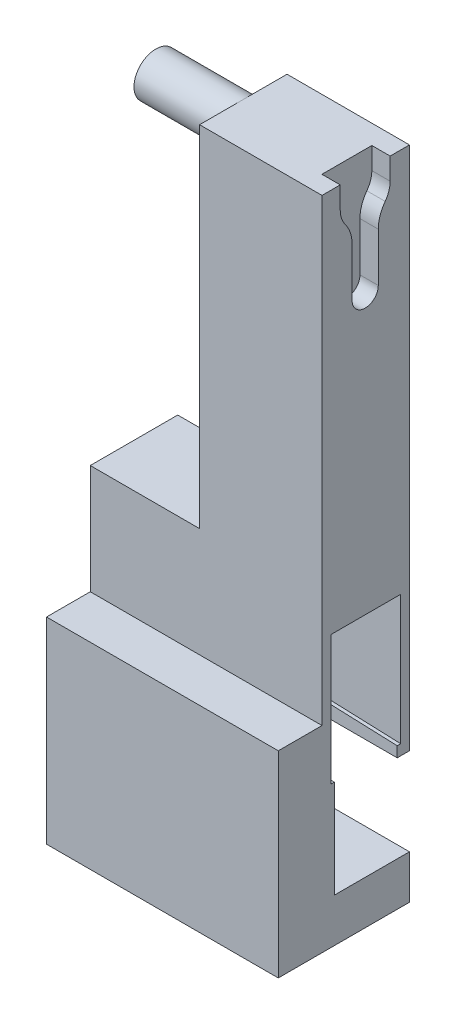
SolidWorks part; units mm, degrees
ref_plane "Front Plane" through (0, 0, 0) normal (0, 0, 1) x (1, 0, 0)
ref_plane "Top Plane" through (0, 0, 0) normal (0, 1, 0) x (1, 0, 0)
ref_plane "Right Plane" through (0, 0, 0) normal (1, 0, 0) x (0, 0, -1)
sketch "Sketch1" plane through (0, 0, 0) normal (0, 1, 0) x (1, 0, 0)
  line L1 (-17.78, -12.7) -> (17.78, -12.7)
  line L2 (-17.78, -12.7) -> (-17.78, 12.7)
  line L3 (-17.78, 12.7) -> (17.78, 12.7)
  line L4 (17.78, -12.7) -> (17.78, 12.7)
  line L5 (-17.78, -12.7) -> (17.78, 12.7) construction
  line L6 (-17.78, 12.7) -> (17.78, -12.7) construction
  point P0 (0, 0)
  dimension "D1" = 25.4
  dimension "D2" = 35.56
extrude "Boss-Extrude1" add sketch "Sketch1" along normal mid plane 50.8
sketch "Sketch2" plane through (-17.78, 0, 0) normal (-1, 0, 0) x (0, 0, 1)
  line L0 (-12.7, 25.4) -> (12.7, 25.4) construction
  circle A0 centre (0, 19.05) radius 6.35
  dimension "D1" = 12.7
extrude "Boss-Extrude2" add sketch "Sketch2" along normal mid plane 50.8
sketch "Sketch7" plane through (0, -25.4, 0) normal (0, -1, 0) x (1, 0, 0)
  line L1 (-17.78, 12.7) -> (17.78, 12.7)
  line L2 (-17.78, 12.7) -> (-17.78, -12.7)
  line L3 (-17.78, -12.7) -> (17.78, -12.7)
  line L4 (17.78, 12.7) -> (17.78, -12.7)
extrude "Boss-Extrude3" add sketch "Sketch7" along normal blind 101.6
sketch "Sketch10" plane through (-17.78, 0, 0) normal (-1, 0, 0) x (0, 0, 1)
  line L0 (12.7, 25.4) -> (12.7, -127) construction
  line L1 (-12.7, -127) -> (12.7, -127)
  line L2 (-12.7, -127) -> (-12.7, -76.2)
  line L3 (-12.7, -76.2) -> (12.7, -76.2)
  line L4 (12.7, -127) -> (12.7, -76.2)
  dimension "D1" = 50.8
extrude "Boss-Extrude4" add sketch "Sketch10" along normal blind 31.75
sketch "Sketch11" plane through (17.78, 0, 0) normal (1, 0, 0) x (0, 0, -1)
  line L0 (12.7, 25.4) -> (12.7, -127) construction
  line L1 (-12.7, -127) -> (12.7, -127)
  line L2 (-12.7, -127) -> (-12.7, -76.2)
  line L3 (-12.7, -76.2) -> (12.7, -76.2)
  line L4 (12.7, -127) -> (12.7, -76.2)
  line L5 (-10.16, -123.952) -> (-12.7, -127) construction
  line L6 (-10.16, -123.952) -> (10.16, -123.952)
  line L7 (-10.16, -123.952) -> (-10.16, -86.36)
  line L8 (-10.16, -86.36) -> (10.16, -86.36)
  line L9 (10.16, -123.952) -> (10.16, -86.36)
  line L10 (10.16, -123.952) -> (12.7, -127) construction
  dimension "D1" = 50.8
  dimension "D2" = 3.048
  dimension "D3" = 20.32
  dimension "D4" = 37.592
extrude "Cut-Extrude3" cut sketch "Sketch11" against normal blind 49.53 contours L6 L9 L8 L7 region at (17.78, -105.156, 0)
sketch "Sketch12" plane through (17.78, 0, 0) normal (1, 0, 0) x (0, 0, -1)
  line L0 (-3.96, 8.728) -> (-3.96, -5.422) construction
  line L1 (3.64, -5.422) -> (3.64, 8.728) construction
  line L2 (-3.96, 8.728) -> (-3.96, -5.422)
  line L3 (3.64, -5.422) -> (3.64, 8.728)
  line L4 (7.09, 19.078) -> (7.09, 26.328)
  line L5 (7.09, 26.328) -> (-0.16, 26.328)
  line L6 (-7.41, 19.078) -> (-7.41, 26.328)
  line L7 (-7.41, 26.328) -> (-0.16, 26.328)
  arc A0 (5.64, 14.728) -> (0.34, 26.3107) centre (-0.16, 19.078) ccw construction
  arc A1 (-0.66, 26.3107) -> (-5.96, 14.728) centre (-0.16, 19.078) ccw construction
  arc A2 (-3.96, 8.728) -> (-5.96, 14.728) centre (-13.96, 8.728) ccw construction
  arc A3 (-3.96, -5.422) -> (3.64, -5.422) centre (-0.16, -5.422) ccw construction
  arc A4 (5.64, 14.728) -> (3.64, 8.728) centre (13.64, 8.728) ccw construction
  arc A5 (5.64, 14.728) -> (-0.16, 26.328) centre (-0.16, 19.078) ccw
  arc A6 (-0.16, 26.328) -> (-5.96, 14.728) centre (-0.16, 19.078) ccw
  arc A7 (-3.96, 8.728) -> (-5.96, 14.728) centre (-13.96, 8.728) ccw
  arc A8 (-3.96, -5.422) -> (3.64, -5.422) centre (-0.16, -5.422) ccw
  arc A9 (5.64, 14.728) -> (3.64, 8.728) centre (13.64, 8.728) ccw
  circle A10 centre (-0.16, -5.422) radius 1.3954 construction
  circle A11 centre (-0.16, -1.422) radius 1.3954 construction
  circle A12 centre (-0.16, -5.422) radius 1.3954
  circle A13 centre (-0.16, -1.422) radius 1.3954
  line M15 (12.7, 25.4) -> (-12.7, 25.4)
extrude "Cut-Extrude4" cut sketch "Sketch12" against normal up to surface (5.32 mm away) contours A9 A5 A6 A7 L2 A8 L3 M15 | A6 L6 M15 | A5 L4 M15 region at (17.78, 11.0681, 0.16) region at (17.78, 23.9112, 6.3737) region at (17.78, 23.9112, -6.0537)
extrude "Cut-Extrude5" cut sketch "Sketch12<3>" against normal offset from surface (11.67 mm away) 6.35 contours A13 | A12 region at (17.78, -5.422, 0.16) region at (17.78, -1.422, 0.16) up to face at (12.46, -2.8174, 0.16)
sketch "Sketch12<3>" plane through (17.78, 0, 0) normal (1, 0, 0) x (0, 0, -1) same geometry as "Sketch12"
sketch "Sketch14" plane through (0, 0, -10.16) normal (0, 0, 1) x (1, 0, 0)
  line L0 (17.78, -123.952) -> (-31.75, -123.952)
  line L1 (-31.75, -123.952) -> (-31.75, -122.0925)
  line L2 (-31.75, -123.952) -> (-31.75, -86.36) construction
  line L3 (-31.75, -122.0925) -> (17.78, -123.952)
  dimension "D1" = 177.85
extrude "Boss-Extrude5" add sketch "Sketch14" along normal up to surface (20.32 mm away) up to face at (-6.985, -105.156, 10.16)
sketch "Sketch16" plane through (17.78, 0, 0) normal (1, 0, 0) x (0, 0, -1)
  line L0 (-10.16, -123.952) -> (-10.16, -127) construction
  line L1 (12.7, -127) -> (-12.7, -127) construction
  line L2 (-10.16, -122.0925) -> (10.16, -122.0925) construction
  line L3 (-9.144, -122.0925) -> (9.144, -122.0925)
  line L4 (-9.144, -122.0925) -> (-9.144, -127)
  line L5 (-9.144, -127) -> (9.144, -127)
  line L6 (9.144, -122.0925) -> (9.144, -127)
  line L7 (-10.16, -123.952) -> (-9.144, -123.952) construction
  line L8 (-10.16, -123.952) -> (10.16, -123.952) construction
  line L9 (10.16, -123.952) -> (9.144, -123.952) construction
  dimension "D1" = 1.016
extrude "Cut-Extrude6" cut sketch "Sketch16" against normal blind 45.212
sketch "Sketch18" plane through (-31.75, 0, 0) normal (1, 0, 0) x (0, 0, -1)
  line L15 (-10.16, -122.0925) -> (10.16, -122.0925) construction
  line L18 (-9.398, -115.7425) -> (-0.762, -115.7425)
  line L20 (-9.398, -115.7425) -> (-9.398, -112.4405)
  line L22 (-9.398, -112.4405) -> (9.398, -112.4405)
  line L28 (0.762, -117.7745) -> (-0.762, -117.7745)
  line L33 (9.398, -115.7425) -> (9.398, -112.4405)
  line L34 (-9.398, -115.7425) -> (-10.16, -115.7425) construction
  line L35 (-10.16, -123.952) -> (-10.16, -86.36) construction
  line L36 (9.398, -115.7425) -> (10.16, -115.7425) construction
  line L37 (10.16, -123.952) -> (10.16, -86.36) construction
  line L38 (0.762, -117.7745) -> (0.762, -115.7425)
  line L39 (-0.762, -117.7745) -> (-0.762, -115.7425)
  line L40 (0.762, -115.7425) -> (9.398, -115.7425)
  dimension "D1" = 6.35
  dimension "D2" = 2.032
  dimension "D3" = 18.796
  dimension "D4" = 1.524
  dimension "D5" = 3.302
extrude "Cut-Extrude7" cut sketch "Sketch18" against normal blind 7.62
sketch "Sketch19" plane through (0, 0, 12.7) normal (0, 0, 1) x (1, 0, 0)
  line L0 (17.78, 25.4) -> (17.78, -127) construction
  line L1 (-49.53, -127) -> (17.78, -127)
  line L2 (-49.53, -127) -> (-49.53, -107.95)
  line L3 (-49.53, -107.95) -> (17.78, -107.95)
  line L4 (17.78, -127) -> (17.78, -107.95)
  dimension "D1" = 19.05
extrude "Boss-Extrude6" add sketch "Sketch19" along normal blind 12.7
sketch "Sketch20" plane through (0, -127, 0) normal (0, -1, 0) x (1, 0, 0)
  line L1 (-27.432, 9.144) -> (17.78, 9.144)
  line L2 (17.78, 9.144) -> (17.78, 25.4)
  line L3 (17.78, 25.4) -> (-49.53, 25.4)
  line L7 (-27.432, 9.144) -> (-49.53, -12.7)
  line L8 (-49.53, -12.7) -> (-49.53, 25.4)
extrude "Boss-Extrude7" add sketch "Sketch20" along normal blind 38.1
sketch "Sketch21" plane through (0, 0, 9.144) normal (0, 0, -1) x (-1, 0, 0)
  line L0 (49.53, -165.1) -> (49.53, -127) construction
  line L1 (-17.78, -165.1) -> (49.53, -165.1)
  line L2 (-17.78, -165.1) -> (-17.78, -152.4)
  line L3 (-17.78, -152.4) -> (49.53, -152.4)
  line L4 (49.53, -165.1) -> (49.53, -152.4)
  dimension "D1" = 12.7
extrude "Boss-Extrude8" add sketch "Sketch21" along normal up to vertex (21.844 mm away) up to point (-49.53, -165.1, -12.7)
sketch "Sketch22" plane through (0, -152.4, 0) normal (0, 1, 0) x (1, 0, 0)
  arc A0 (-1.15, -4.129) -> (-1.15, 3.909) centre (-1.65, -0.11) ccw construction
  arc A1 (-1.15, -4.129) -> (-1.15, 3.909) centre (-1.65, -0.11) ccw construction
  circle A2 centre (-1.65, -0.11) radius 4.05
extrude "Cut-Extrude8" cut sketch "Sketch22" against normal blind 2.54
